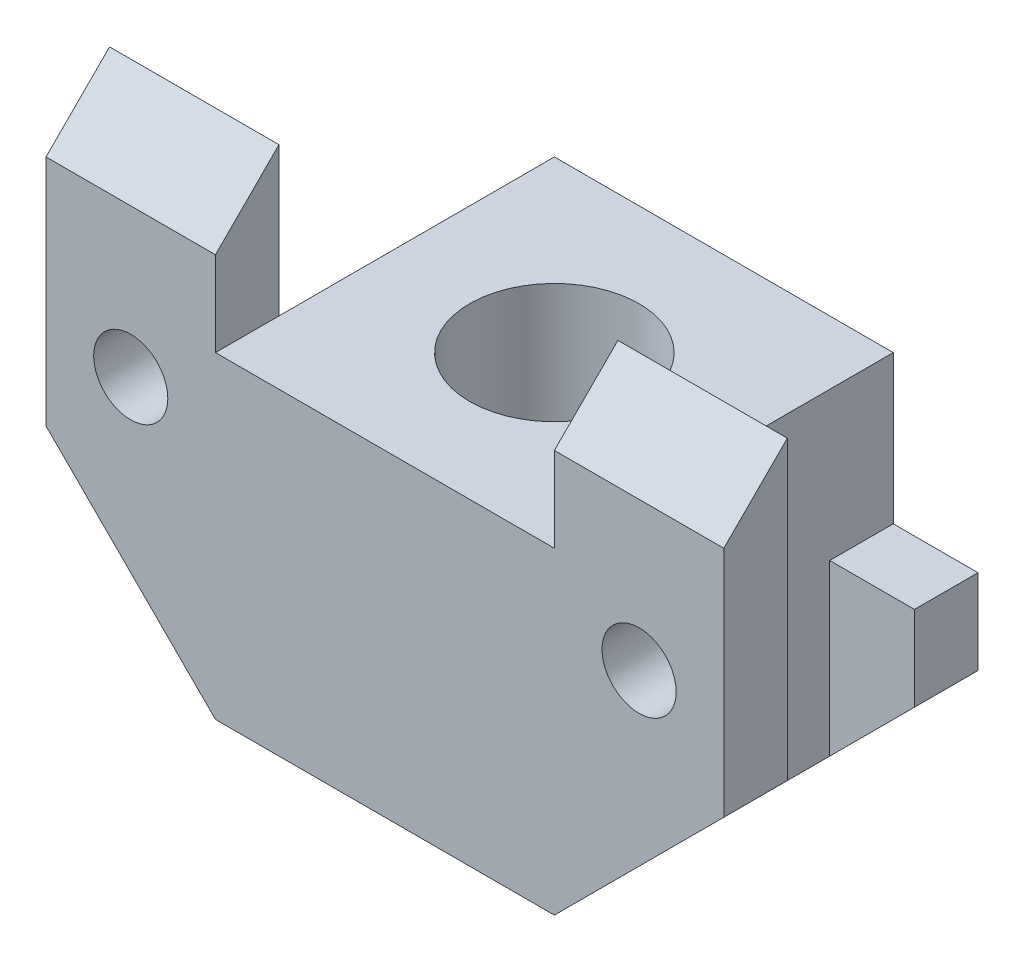
SolidWorks part; units mm, degrees
material "PETG"
ref_plane "Front Plane" through (0, 0, 0) normal (0, 0, 1) x (1, 0, 0)
ref_plane "Top Plane" through (0, 0, 0) normal (0, 1, 0) x (1, 0, 0)
ref_plane "Right Plane" through (0, 0, 0) normal (1, 0, 0) x (0, 0, -1)
sketch "Sketch1" plane through (0, 0, 0) normal (0, 1, 0) x (1, 0, 0)
  line L0 (0, 0) -> (0, 50000) construction
  line L2 (-8, -5) -> (-8, 5)
  line L4 (8, -5) -> (8, 5)
  line L5 (-8, -5) -> (8, 5) construction
  line L6 (-8, 5) -> (8, -5) construction
  line L7 (-16, 8) -> (16, 8)
  line L8 (-16, 8) -> (-16, 5)
  line L9 (-16, 5) -> (-8, 5)
  line L10 (16, 8) -> (16, 5)
  line L11 (-16, 8) -> (16, 5) construction
  line L12 (-16, 5) -> (16, 8) construction
  line L13 (-16, -8) -> (16, -8)
  line L14 (-16, -8) -> (-16, -5)
  line L15 (-16, -5) -> (-8, -5)
  line L16 (16, -8) -> (16, -5)
  line L17 (-16, -8) -> (16, -5) construction
  line L18 (-16, -5) -> (16, -8) construction
  line L19 (8, -5) -> (16, -5)
  line L21 (8, 5) -> (16, 5)
  circle A0 centre (0, 0) radius 4
  point P7 (0, 6.5)
  point P12 (0, -6.5)
  point P17 (0, 0)
  point P20 (1.9399, -6.879)
  point P21 (0, 0)
  point P22 (0, 7.8167)
  dimension "D1" = 8
  dimension "D2" = 16
  dimension "D3" = 10
  dimension "D4" = 8
  dimension "D5" = 3
extrude "Boss-Extrude1" add sketch "Sketch1" along normal blind 15
chamfer "Chamfer1" distance 8 angle 45 4 edges at (16, 0, 6.5) (-16, 0, 6.5) (-16, 0, -6.5) (16, 0, -6.5)
sketch "Sketch2" plane through (0, 15, 0) normal (0, 1, 0) x (1, 0, 0)
  line L1 (16, -8) -> (8, -8)
  line L2 (16, -8) -> (16, -5)
  line L3 (16, -5) -> (8, -5)
  line L4 (8, -8) -> (8, -5)
  line L5 (16, 8) -> (8, 8)
  line L6 (16, 8) -> (16, 5)
  line L7 (16, 5) -> (8, 5)
  line L8 (8, 8) -> (8, 5)
  line L9 (-16, -8) -> (-8, -8)
  line L10 (-16, -8) -> (-16, -5)
  line L11 (-16, -5) -> (-8, -5)
  line L12 (-8, -8) -> (-8, -5)
  line L13 (-16, 8) -> (-8, 8)
  line L14 (-16, 8) -> (-16, 5)
  line L15 (-16, 5) -> (-8, 5)
  line L16 (-8, 8) -> (-8, 5)
extrude "Boss-Extrude2" add sketch "Sketch2" along normal blind 7
chamfer "Chamfer3" distance 3 angle 45 4 edges at (-12, 22, 8) (12, 22, 8) (-12, 22, -8) (12, 22, -8)
sketch "Sketch4" plane through (0, 15, 0) normal (0, 1, 0) x (1, 0, 0)
  line L1 (16, 5) -> (-16, 5)
  line L2 (16, 5) -> (16, 8)
  line L3 (16, 8) -> (-16, 8)
  line L4 (-16, 5) -> (-16, 8)
extrude "Cut-Extrude2" cut sketch "Sketch4" against normal blind 7 and the other way up to next body kept at (-16, 8, -5)
sketch "Sketch5" plane through (0, 0, -8) normal (0, 0, -1) x (-1, 0, 0)
  line L0 (0, 0) -> (0, 50000) construction
  line L1 (-8, 0) -> (8, 0) construction
  line L2 (-12, 4) -> (-12, 8)
  line L3 (-16, 8) -> (-8, 0) construction
  line L4 (-16, 8) -> (16, 8) construction
  line L5 (-12, 8) -> (-16, 8)
  line L6 (-16, 8) -> (-12, 4)
  line L7 (16, 8) -> (12, 4)
  line L8 (12, 8) -> (16, 8)
  line L9 (12, 4) -> (12, 8)
  point P4 (0, 0)
  dimension "D1" = 12
extrude "Cut-Extrude3" cut sketch "Sketch5" against normal up to next
sketch "Sketch6" plane through (0, 0, 8) normal (0, 0, 1) x (1, 0, 0)
  line L0 (-8, 15) -> (8, 15) construction
  line L1 (16, 19) -> (16, 8) construction
  line L2 (0, 0) -> (0, 50000) construction
  line L3 (-8, 0) -> (8, 0) construction
  circle A0 centre (12, 12) radius 1.75
  circle A1 centre (-12, 12) radius 1.75
  point P10 (0, 0)
  dimension "D1" = 3.5
  dimension "D2" = 3
  dimension "D3" = 4
extrude "Cut-Extrude4" cut sketch "Sketch6" against normal through all
sketch "Sketch7" plane through (0, 8, 0) normal (0, 1, 0) x (1, 0, 0)
  line L0 (12, 8) -> (-12, 8) construction
  line L1 (8, 5) -> (-8, 5)
  line L2 (8, 5) -> (8, 8)
  line L3 (8, 8) -> (-8, 8)
  line L4 (-8, 5) -> (-8, 8)
  point P7 (0, 0)
extrude "Boss-Extrude3" add sketch "Sketch7" along normal up to surface (7 mm away) up to face at (0, 15, 4)
